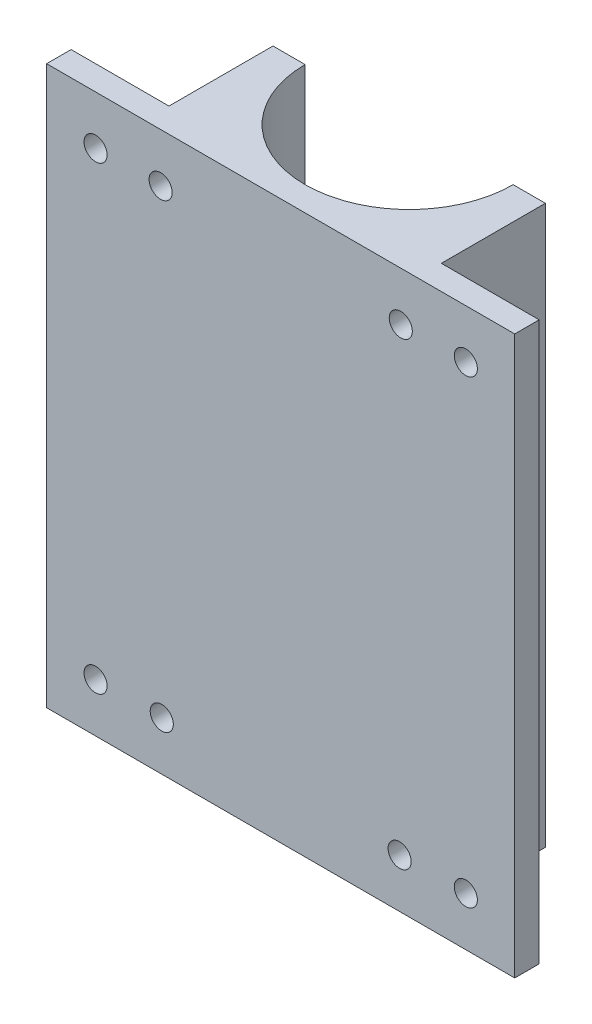
SolidWorks part; units mm, degrees
ref_plane "Front Plane" through (0, 0, 0) normal (0, 0, 1) x (1, 0, 0)
ref_plane "Top Plane" through (0, 0, 0) normal (0, 1, 0) x (1, 0, 0)
ref_plane "Right Plane" through (0, 0, 0) normal (1, 0, 0) x (0, 0, -1)
sketch "Sketch1" plane through (0, 0, 0) normal (0, 1, 0) x (1, 0, 0)
  line L1 (-23.8485, 17.6982) -> (36.9033, 17.6982)
  line L2 (-23.8485, 17.6982) -> (-23.8485, 14.5232)
  line L3 (-23.8485, 14.5232) -> (36.9033, 14.5232)
  line L4 (36.9033, 17.6982) -> (36.9033, 14.5232)
  line L6 (24.2033, 31.1982) -> (-11.1467, 31.1982)
  line L7 (24.2033, 31.1982) -> (24.2033, 17.6982)
  line L8 (24.2033, 17.6982) -> (-11.1467, 17.6982)
  line L9 (-11.1467, 31.1982) -> (-11.1467, 17.6982)
  line L10 (-6.975, 31.1982) -> (-6.675, 31.1982)
  line L11 (20.025, 31.1982) -> (19.725, 31.1982)
  line L12 (6.5283, 38.6577) -> (6.5283, -0.813) construction
  arc A2 (-6.975, 31.1982) -> (20.025, 31.1982) centre (6.525, 31.1982) ccw
  arc A3 (-6.675, 31.1982) -> (19.725, 31.1982) centre (6.525, 31.1982) ccw
  dimension "D1" = 12.7018
  dimension "D2" = 12.7
extrude "Boss-Extrude3" add sketch "Sketch1" along normal blind 72.39 contours A2 L6 L9 L1 | L12 A2 L1 L2 L3 | L1 L12 L3 L4 | A2 L1 L7 L6 region at (-8.6601, 0, -16.1107) region at (-6.9701, 0, -22.9176) region at (20.024, 0, -22.919) region at (21.7158, 0, -16.1107)
extrude "Boss-Extrude4" add sketch "Sketch1<13>" along normal blind 51.39 contours A2 L11 A3 L10
sketch "Sketch1<13>" plane through (0, 0, 0) normal (0, 1, 0) x (1, 0, 0) same geometry as "Sketch1"
hole_wizard "Ø3.0mm Dowel Hole1" positions "Sketch4" profile "Sketch5" hole size "Ø3.0" standard "ANSI Metric" end condition through all
sketch "Sketch4" plane through (0, 0, -17.6982) normal (0, 0, -1) x (-1, 0, 0)
  line L0 (-24.2033, 72.39) -> (-36.9033, 72.39) construction
  line L1 (-36.9033, 72.39) -> (-36.9033, 0) construction
  line L3 (-24.2033, 0) -> (-36.9033, 0) construction
  point P0 (-30.5533, 66.04)
  point P9 (-30.5533, 6.35)
  point P12 (0, 0)
  point P15 (0, 0)
  point P16 (0, 0)
  point P19 (0, 0)
  point P20 (-30.5533, 0)
  dimension "D1" = 6.35
  dimension "D2" = 6.35
  dimension "D3" = 6.35
  dimension "D4" = 6.35
sketch "Sketch5" plane through (30.5533, 66.04, -17.6982) normal (1, 0, 0) x (0, 1, 0)
  line L0 (0, 0) -> (0, 3.175)
  line L1 (0, 3.175) -> (1.5, 3.175)
  line L2 (1.5, 3.175) -> (1.5, 0)
  line L5 (1.5, 0) -> (0, 0)
  line L11 (0, -6.35) -> (0, 107.95) construction
  dimension "Thru Hole Dia." = 3
  dimension "Thru Hole Depth" = 3.175
hole_wizard "Ø3.0mm Dowel Hole2" positions "Sketch6" profile "Sketch7" hole size "Ø3.0" standard "ANSI Metric" end condition through all
sketch "Sketch6" plane through (0, 0, -17.6982) normal (0, 0, -1) x (-1, 0, 0)
  line L0 (23.8485, 72.39) -> (11.1467, 72.39) construction
  line L1 (23.8485, 72.39) -> (23.8485, 0) construction
  line L2 (23.8485, 0) -> (11.1467, 0) construction
  point P0 (17.4985, 6.35)
  point P2 (17.4985, 66.04)
  point P19 (0, 0)
  point P20 (0, 0)
  point P21 (0, 0)
  point P22 (0, 0)
  dimension "D1" = 6.35
  dimension "D2" = 6.35
  dimension "D3" = 6.35
  dimension "D4" = 6.35
sketch "Sketch7" plane through (-17.4985, 6.35, -17.6982) normal (1, 0, 0) x (0, 1, 0)
  line L0 (0, 0) -> (0, 3.175)
  line L1 (0, 3.175) -> (1.5, 3.175)
  line L2 (1.5, 3.175) -> (1.5, 0)
  line L5 (1.5, 0) -> (0, 0)
  line L11 (0, -6.35) -> (0, 107.95) construction
  dimension "Thru Hole Dia." = 3
  dimension "Thru Hole Depth" = 3.175
hole_wizard "Ø3.0mm Dowel Hole4" positions "Sketch10" profile "Sketch11" hole size "Ø3.0" standard "ANSI Metric" end condition through all
sketch "Sketch10" plane through (0, 0, -31.1982) normal (0, 0, -1) x (-1, 0, 0)
  line L2 (-42.513, 66.04) -> (28.1638, 66.04) construction
  line L4 (-43.5181, 6.35) -> (29.2845, 6.35) construction
  line L6 (-24.2033, 72.39) -> (-24.2033, 0) construction
  line L7 (11.1467, 72.39) -> (11.1467, 0) construction
  line L8 (-24.2033, 72.39) -> (-24.2033, 0) construction
  line L9 (11.1467, 72.39) -> (11.1467, 0) construction
  point P0 (-22.1133, 66.04)
  point P2 (9.0567, 66.04)
  point P4 (8.9067, 6.35)
  point P5 (-21.9633, 6.35)
  point P29 (0, 0)
  point P30 (0, 0)
  dimension "D1" = 2.24
  dimension "D2" = 2.24
  dimension "D3" = 2.09
  dimension "D4" = 2.09
sketch "Sketch11" plane through (22.1133, 66.04, -31.1982) normal (1, 0, 0) x (0, 1, 0)
  line L0 (0, 0) -> (0, 16.675)
  line L1 (0, 16.675) -> (1.5, 16.675)
  line L2 (1.5, 16.675) -> (1.5, 0)
  line L5 (1.5, 0) -> (0, 0)
  line L11 (0, -6.35) -> (0, 107.95) construction
  dimension "Thru Hole Dia." = 3
  dimension "Thru Hole Depth" = 16.675
